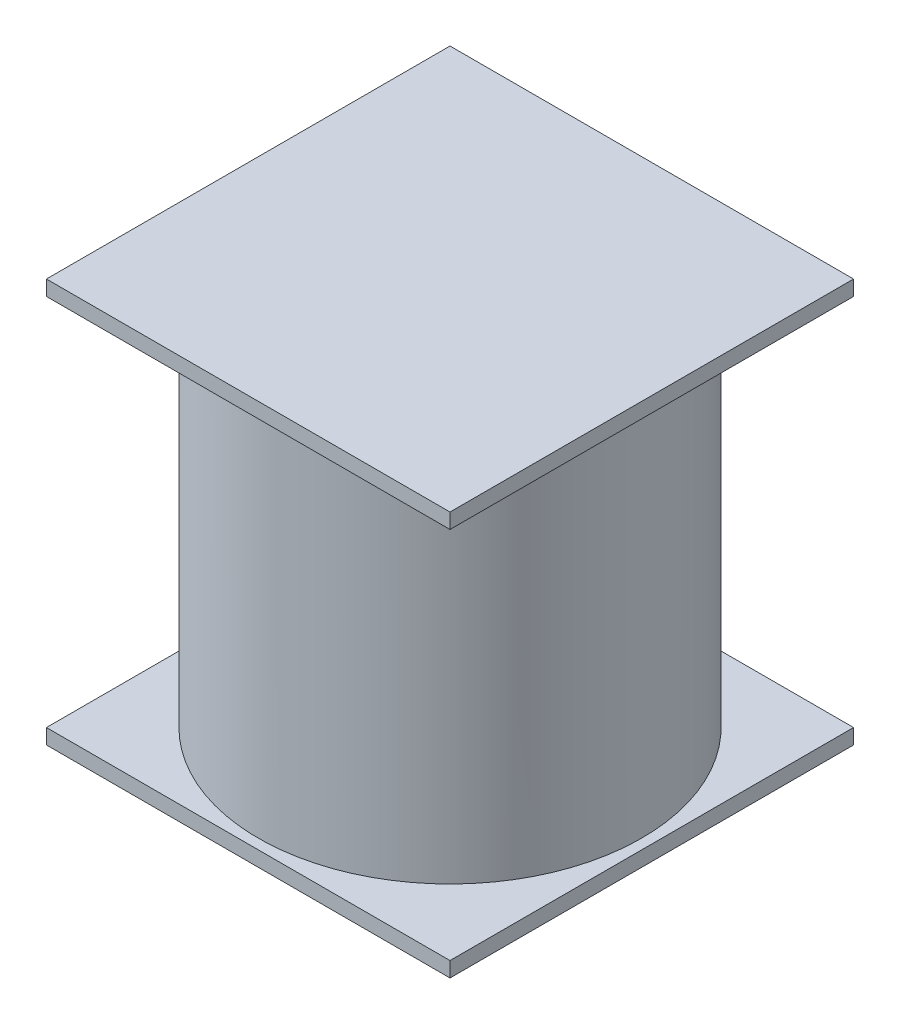
SolidWorks part; units mm, degrees
ref_plane "Front Plane" through (0, 0, 0) normal (0, 0, 1) x (1, 0, 0)
ref_plane "Top Plane" through (0, 0, 0) normal (0, 1, 0) x (1, 0, 0)
ref_plane "Right Plane" through (0, 0, 0) normal (1, 0, 0) x (0, 0, -1)
sketch "Sketch1" plane through (0, 0, 0) normal (0, 1, 0) x (1, 0, 0)
  line L1 (0, 0) -> (80, 0)
  line L2 (0, 0) -> (0, 80)
  line L3 (0, 80) -> (80, 80)
  line L4 (80, 0) -> (80, 80)
  dimension "D1" = 80
  dimension "D2" = 80
extrude "Boss-Extrude1" add sketch "Sketch1" along normal blind 3
sketch "Sketch3" plane through (0, 3, 0) normal (0, 1, 0) x (1, 0, 0)
  line L0 (80, 80) -> (0, 80) construction
  line L1 (0, 80) -> (0, 0) construction
  circle A0 centre (40, 40) radius 38
  dimension "D3" = 76
  dimension "D1" = 40
  dimension "D2" = 40
extrude "Extrude-Thin1" add sketch "Sketch3" along normal blind 74 thin thin type one direction reverse wall 3
sketch "Sketch5" plane through (0, 77, 0) normal (0, 1, 0) x (1, 0, 0)
  line L0 (80, 0) -> (80, 80) construction
  line L1 (80, 0) -> (0, 0)
  line L2 (80, 0) -> (80, 80)
  line L3 (80, 80) -> (0, 80)
  line L4 (0, 0) -> (0, 80)
  line L5 (0, 0) -> (80, 0) construction
  dimension "D1" = 80
  dimension "D2" = 80
  dimension "D3" = 0
  dimension "D4" = 0
extrude "Boss-Extrude2" add sketch "Sketch5" along normal blind 3
